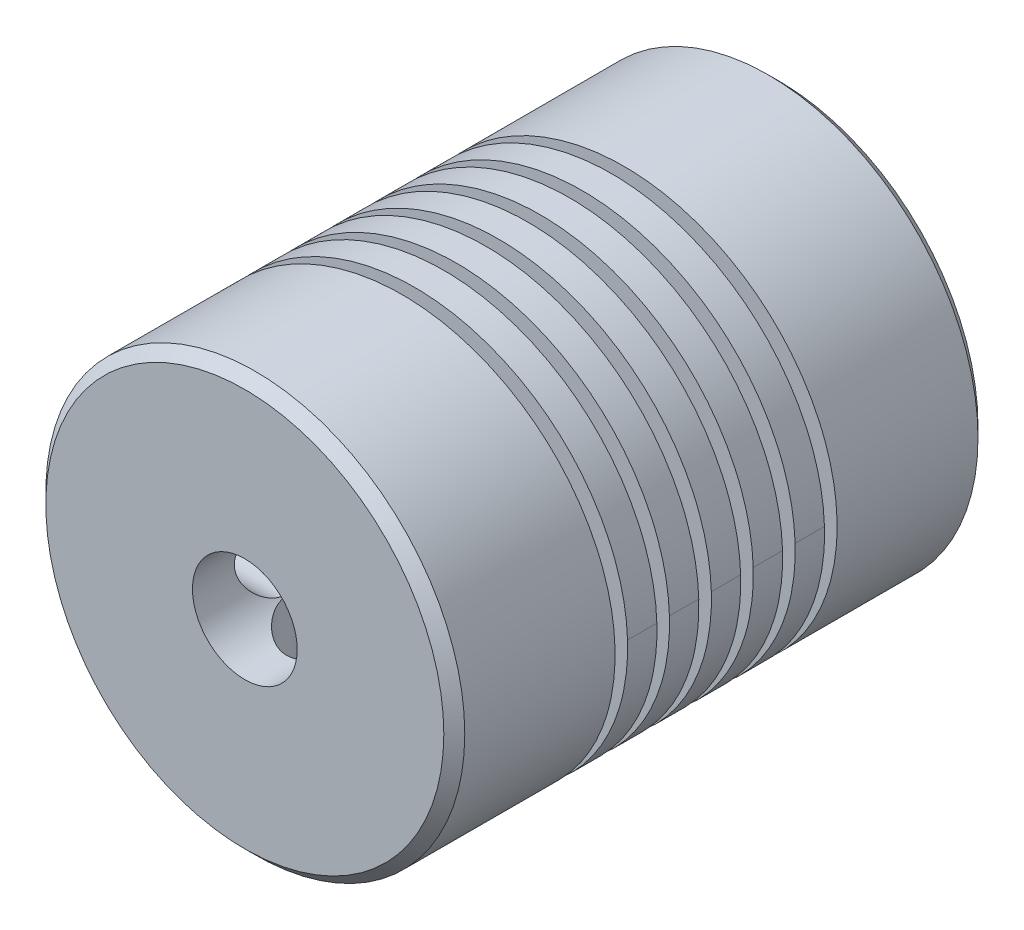
SolidWorks part; units mm, degrees
material "Сплав 1060"
ref_plane "Спереди" through (0, 0, 0) normal (0, 0, 1) x (1, 0, 0)
ref_plane "Сверху" through (0, 0, 0) normal (0, 1, 0) x (1, 0, 0)
ref_plane "Справа" through (0, 0, 0) normal (1, 0, 0) x (0, 0, -1)
sketch "Эскиз1" plane through (0, 0, 0) normal (0, 0, 1) x (1, 0, 0)
  circle A0 centre (0, 0) radius 10
  circle A1 centre (0, 0) radius 2.5
  dimension "D1" = 20
  dimension "D2" = 5
extrude "Бобышка-Вытянуть1" add sketch "Эскиз1" along normal mid plane 25.5
sketch "Эскиз3" plane through (0, 0, 0) normal (0, 1, 0) x (1, 0, 0)
  line L0 (0, 9) -> (0, -9) construction
  circle A0 centre (0, 9) radius 1.75
  circle A1 centre (0, -9) radius 1.75
  dimension "D1" = 3.5
  dimension "D2" = 18
extrude "Вырез-Вытянуть2" cut sketch "Эскиз3" against normal through all
sketch "Эскиз4" plane through (0, 0, 0) normal (1, 0, 0) x (0, 0, -1)
  line L0 (-9, 0) -> (9, 0) construction
  circle A0 centre (-9, 0) radius 1.75
  circle A1 centre (9, 0) radius 1.75
  dimension "D2" = 3.5
  dimension "D1" = 18
extrude "Вырез-Вытянуть3" cut sketch "Эскиз4" against normal through all
ref_plane "Плоскость1" through (0, 0, -6.25) normal (0, 0, -1) x (-1, 0, 0)
sketch "Эскиз6" plane through (0, 0, -6.25) normal (0, 0, -1) x (-1, 0, 0)
  circle A0 centre (0, 0) radius 12.5
  dimension "D1" = 25
curve "Спираль1" pitch 2 height 12 radius 12.5 centre (0, 0, -6.25) axis (0, 0, 1) start towards (-1, 0, 0)
sketch "Эскиз7" plane through (0, 0, 0) normal (0, 1, 0) x (1, 0, 0)
  line L1 (-12.442, 5.9196) -> (-2, 5.9196)
  line L2 (-12.442, 5.9196) -> (-12.442, 6.5196)
  line L3 (-12.442, 6.5196) -> (-2, 6.5196)
  line L4 (-2, 5.9196) -> (-2, 6.5196)
  spline S0 degree 3 poles (-12.5, 6.25) (-12.5, 6.2086) (-11.8491, 6.1249) (-9.0689, 6) (-4.9081, 5.875) (0, 5.75) (4.9081, 5.625) (9.0689, 5.5) (11.8491, 5.375) (12.8254, 5.25) (11.8491, 5.125) (9.0689, 5) (4.9081, 4.875) (0, 4.75) (-4.9081, 4.625) (-9.0689, 4.5) (-11.8491, 4.375) (-12.8254, 4.25) (-11.8491, 4.125) (-9.0689, 4) (-4.9081, 3.875) (0, 3.75) (4.9081, 3.625) (9.0689, 3.5) (11.8491, 3.375) (12.8254, 3.25) (11.8491, 3.125) (9.0689, 3) (4.9081, 2.875) (0, 2.75) (-4.9081, 2.625) (-9.0689, 2.5) (-11.8491, 2.375) (-12.8254, 2.25) (-11.8491, 2.125) (-9.0689, 2) (-4.9081, 1.875) (0, 1.75) (4.9081, 1.625) (9.0689, 1.5) (11.8491, 1.375) (12.8254, 1.25) (11.8491, 1.125) (9.0689, 1) (4.9081, 0.875) (0, 0.75) (-4.9081, 0.625) (-9.0689, 0.5) (-11.8491, 0.375) (-12.8254, 0.25) (-11.8491, 0.125) (-9.0689, 0) (-4.9081, -0.125) (0, -0.25) (4.9081, -0.375) (9.0689, -0.5) (11.8491, -0.625) (12.8254, -0.75) (11.8491, -0.875) (9.0689, -1) (4.9081, -1.125) (0, -1.25) (-4.9081, -1.375) (-9.0689, -1.5) (-11.8491, -1.625) (-12.8254, -1.75) (-11.8491, -1.875) (-9.0689, -2) (-4.9081, -2.125) (0, -2.25) (4.9081, -2.375) (9.0689, -2.5) (11.8491, -2.625) (12.8254, -2.75) (11.8491, -2.875) (9.0689, -3) (4.9081, -3.125) (0, -3.25) (-4.9081, -3.375) (-9.0689, -3.5) (-11.8491, -3.625) (-12.8254, -3.75) (-11.8491, -3.875) (-9.0689, -4) (-4.9081, -4.125) (0, -4.25) (4.9081, -4.375) (9.0689, -4.5) (11.8491, -4.625) (12.8254, -4.75) (11.8491, -4.875) (9.0689, -5) (4.9081, -5.125) (0, -5.25) (-4.9081, -5.375) (-9.0689, -5.5) (-11.8491, -5.6249) (-12.5, -5.7086) (-12.5, -5.75) knots 0 0 0 0 0.010417 0.020833 0.03125 0.041667 0.052083 0.0625 0.072917 0.083333 0.09375 0.104167 0.114583 0.125 0.135417 0.145833 0.15625 0.166667 0.177083 0.1875 0.197917 0.208333 0.21875 0.229167 0.239583 0.25 0.260417 0.270833 0.28125 0.291667 0.302083 0.3125 0.322917 0.333333 0.34375 0.354167 0.364583 0.375 0.385417 0.395833 0.40625 0.416667 0.427083 0.4375 0.447917 0.458333 0.46875 0.479167 0.489583 0.5 0.510417 0.520833 0.53125 0.541667 0.552083 0.5625 0.572917 0.583333 0.59375 0.604167 0.614583 0.625 0.635417 0.645833 0.65625 0.666667 0.677083 0.6875 0.697917 0.708333 0.71875 0.729167 0.739583 0.75 0.760417 0.770833 0.78125 0.791667 0.802083 0.8125 0.822917 0.833333 0.84375 0.854167 0.864583 0.875 0.885417 0.895833 0.90625 0.916667 0.927083 0.9375 0.947917 0.958333 0.96875 0.979167 0.989583 1 1 1 1 construction
  point P4 (-12.442, 6.2196)
  dimension "D1" = 0.6
  dimension "D2" = 2
sweep "Вырез-По траектории1" cut profiles "Эскиз7" path "Спираль1" align with end faces yes
chamfer "Фаска1" distance 0.5 angle 45 2 edges at (10, 0, -12.75) (10, 0, 12.75)
sketch "Эскиз8" plane through (0, 0, 0) normal (0, 1, 0) x (1, 0, 0)
  line L0 (-5, 12.75) -> (-5, -2.75)
  line L1 (9.5, 12.75) -> (-9.5, 12.75) construction
  line L2 (-5, -2.75) -> (0, -5.6368)
  line L3 (0, -5.6368) -> (0, 12.75)
  line L4 (0, 12.75) -> (-5, 12.75)
  dimension "D1" = 5
  dimension "D2" = 15.5
  dimension "D3" = 60
revolve "Вырез-Повернуть1" cut sketch "Эскиз8" angle 360 about L3
